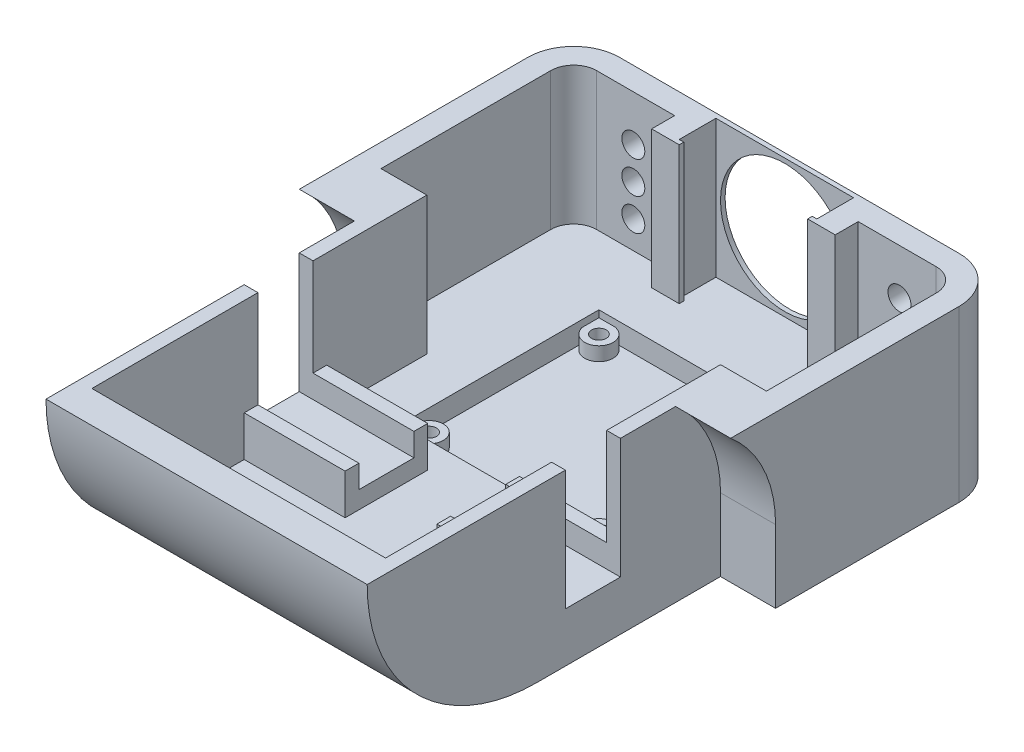
SolidWorks part; units mm, degrees
ref_plane "Front Plane" through (0, 0, 0) normal (0, 0, 1) x (1, 0, 0)
ref_plane "Top Plane" through (0, 0, 0) normal (0, 1, 0) x (1, 0, 0)
ref_plane "Right Plane" through (0, 0, 0) normal (1, 0, 0) x (0, 0, -1)
sketch "Sketch1" plane through (0, 0, 0) normal (0, 1, 0) x (1, 0, 0)
  line L0 (-18.5, 18.5) -> (-18.5, -18.5) construction
  line L1 (-18.5, -18.5) -> (18.5, -18.5) construction
  line L2 (18.5, -18.5) -> (18.5, 18.5) construction
  line L3 (18.5, 18.5) -> (-18.5, 18.5) construction
  line L4 (-21.5, 21.5) -> (-21.5, -21.5) construction
  line L5 (-21.5, -21.5) -> (21.5, -21.5) construction
  line L6 (21.5, -21.5) -> (21.5, 21.5) construction
  line L7 (-18.5, 18.5) -> (-21.5, 21.5) construction
  line L8 (-21.5, 21.5) -> (21.5, 21.5) construction
  line L9 (-18.5, -18.5) -> (-21.5, -21.5) construction
  line L10 (18.5, -18.5) -> (21.5, -21.5) construction
  line L11 (-18.5, 18.5) -> (0, 0) construction
  line L12 (0, 0) -> (18.5, -18.5) construction
  line L13 (-18.5, -18.5) -> (0, 0) construction
  line L14 (-35, -8.5) -> (-35, -48.5)
  line L15 (-35, -48.5) -> (35, -48.5)
  line L16 (35, -48.5) -> (35, -8.5)
  line L17 (35, -8.5) -> (47, -8.5)
  line L18 (47, -8.5) -> (47, 31.5)
  line L19 (-35, -8.5) -> (-47, -8.5)
  line L20 (-47, -8.5) -> (-47, 31.5)
  line L21 (-35, -8.5) -> (-21.5, 21.5) construction
  line L22 (21.5, 21.5) -> (35, -8.5) construction
  line L23 (-37, 41.5) -> (37, 41.5)
  line L24 (-21.6, -21.6) -> (21.6, -21.6)
  line L25 (21.6, -21.6) -> (21.6, 21.6)
  line L26 (-21.6, 21.6) -> (21.6, 21.6)
  line L27 (-21.6, 21.6) -> (-21.6, -21.6)
  line L28 (-21.5, -17.719) -> (-21.6, -17.719)
  line L29 (-17.719, -21.5) -> (-17.719, -21.6)
  line L30 (17.719, -21.5) -> (17.719, -21.6)
  line L31 (21.5, -17.719) -> (21.6, -17.719)
  line L32 (21.5, 17.719) -> (21.6, 17.719)
  line L33 (17.719, 21.5) -> (17.719, 21.6)
  line L34 (-21.5, 17.719) -> (-21.6, 17.719)
  line L35 (-17.719, 21.5) -> (-17.719, 21.6)
  circle A0 centre (-18.5, 18.5) radius 1.6
  circle A1 centre (18.5, 18.5) radius 1.6
  circle A2 centre (-18.5, -18.5) radius 1.6
  circle A3 centre (18.5, -18.5) radius 1.6
  arc A4 (-17.719, 21.5) -> (-21.5, 17.719) centre (-18.5, 18.5) cw
  arc A5 (-21.5, -17.719) -> (-17.719, -21.5) centre (-18.5, -18.5) cw
  arc A6 (17.719, -21.5) -> (21.5, -17.719) centre (18.5, -18.5) cw
  arc A7 (17.719, 21.5) -> (21.5, 17.719) centre (18.5, 18.5) ccw
  arc A8 (-47, 31.5) -> (-37, 41.5) centre (-37, 31.5) cw
  arc A9 (37, 41.5) -> (47, 31.5) centre (37, 31.5) cw
  dimension "D3" = 3.2
  dimension "D4" = 1.5
  dimension "D7" = 12
  dimension "D8" = 20
  dimension "D9" = 90
  dimension "D10" = 0.1
  dimension "D11" = 50
  dimension "D6" = 10
  dimension "D1" = 37
  dimension "D2" = 43
  dimension "D5" = 70
extrude "Boss-Extrude1" add sketch "Sketch1" against normal blind 7 contours L20 L19 L14 L15 L16 L17 L18 L4 L8 L6 L5 | A4 L8 L4 A0 | A0 | A7 L8 A4 L4 A5 L5 A6 L6 | A5 L4 L5 A2 | A2 | A6 L5 L6 A3 | A3 | L8 A7 L6 A1 | A1 region at (-41, 0, 7.1986) region at (-21.5123, 0, 19.6595) region at (0, 0, 0) region at (17.8067, 0, 21.55) region at (-21.5123, 0, -19.6595) region at (21.55, 0, -17.8067) region at (-18.5, 0, -18.5) region at (18.5, 0, -18.5) region at (-18.5, 0, 18.5) region at (18.5, 0, 18.5)
extrude "Cut-Extrude1" cut sketch "Sketch1<5>" against normal blind 1.5 contours A5 L4 L5 A2 | A2 | A7 L8 A4 L4 A5 L5 A6 L6 | A4 L8 L4 A0 | A0 | L8 A7 L6 A1 | A1 | A6 L5 L6 A3 | A3 region at (-21.5123, 0, 19.6595) region at (0, 0, 0) region at (17.8067, 0, 21.55) region at (-21.5123, 0, -19.6595) region at (21.55, 0, -17.8067) region at (-18.5, 0, -18.5) region at (18.5, 0, -18.5) region at (-18.5, 0, 18.5) region at (18.5, 0, 18.5)
sketch "Sketch1<5>" plane through (0, 0, 0) normal (0, 1, 0) x (1, 0, 0) same geometry as "Sketch1"
extrude "Cut-Extrude2" cut sketch "Sketch1<6>" against normal blind 3 from surface contours A7 L8 A4 L4 A5 L5 A6 L6 | A0 | A1 | A2 | A3 region at (0, 0, 0) region at (-18.5, 0, -18.5) region at (18.5, 0, -18.5) region at (-18.5, 0, 18.5) region at (18.5, 0, 18.5) starting at face at (0, -1.5, 0)
sketch "Sketch1<6>" plane through (0, 0, 0) normal (0, 1, 0) x (1, 0, 0) same geometry as "Sketch1"
sketch "Sketch3" plane through (0, 0, 0) normal (0, 1, 0) x (1, 0, 0)
  line L9 (47, -8.5) -> (47, 31.5) construction
  line L10 (-37, 41.5) -> (37, 41.5) construction
  line L11 (-47, -8.5) -> (-47, 31.5) construction
  line L18 (47, -8.5) -> (47, 31.5)
  line L19 (-37, 41.5) -> (37, 41.5)
  line L20 (-47, -8.5) -> (-47, 31.5)
  line L21 (-47, -8.5) -> (-42, -8.5)
  line L22 (42, -8.5) -> (47, -8.5)
  line L23 (-14, 41.5) -> (-14, 40.5)
  line L24 (-14, 40.5) -> (-15, 40.5)
  line L25 (-15, 40.5) -> (-15, 32.5)
  line L26 (-15, 32.5) -> (-14, 32.5)
  line L27 (-14, 32.5) -> (-14, 31.5)
  line L28 (14, 41.5) -> (14, 40.5)
  line L29 (14, 40.5) -> (15, 40.5)
  line L30 (15, 40.5) -> (15, 32.5)
  line L31 (15, 32.5) -> (14, 32.5)
  line L32 (14, 32.5) -> (14, 31.5)
  line L33 (-37, 31.5) -> (-15, 32.5) construction
  line L34 (15, 32.5) -> (37, 31.5) construction
  line L35 (-14, 31.5) -> (-20, 31.5)
  line L36 (-20, 31.5) -> (-20, 36.5)
  line L37 (-20, 36.5) -> (-37, 36.5)
  line L38 (-42, -8.5) -> (-42, 31.5)
  line L39 (-35, -8.5) -> (-47, -8.5) construction
  line L40 (14, 31.5) -> (20, 31.5)
  line L41 (20, 31.5) -> (20, 36.5)
  line L42 (20, 36.5) -> (37, 36.5)
  line L43 (42, -8.5) -> (42, 31.5)
  arc A6 (47, 31.5) -> (37, 41.5) centre (37, 31.5) ccw construction
  arc A7 (-37, 41.5) -> (-47, 31.5) centre (-37, 31.5) ccw construction
  arc A8 (47, 31.5) -> (37, 41.5) centre (37, 31.5) ccw
  arc A9 (-37, 41.5) -> (-47, 31.5) centre (-37, 31.5) ccw
  arc A10 (-42, 31.5) -> (-37, 36.5) centre (-37, 31.5) cw
  arc A11 (37, 36.5) -> (42, 31.5) centre (37, 31.5) cw
  arc M13 (47, 31.5) -> (37, 41.5) centre (37, 31.5) ccw
  line M14 (37, 41.5) -> (-37, 41.5)
  arc M15 (-37, 41.5) -> (-47, 31.5) centre (-37, 31.5) ccw
  line M16 (-47, 31.5) -> (-47, -8.5)
  line M17 (-47, -8.5) -> (-35, -8.5)
  line M21 (35, -8.5) -> (47, -8.5)
  line M22 (47, -8.5) -> (47, 31.5)
  dimension "D2" = 30
  dimension "D3" = 8
  dimension "D4" = 1
  dimension "D1" = 1
  dimension "D5" = 5
  dimension "D6" = 5
extrude "Boss-Extrude2" add sketch "Sketch3" along normal blind 30 contours L27 L26 L25 L24 L23 L19 M15 M16 M17 | L31 L32 L28 L29 L30 M21 M22 M13 M14 region at (44.5, 0, 7.9009) region at (-14.5991, 0, -41)
sketch "Sketch5" plane through (0, 0, 0) normal (1, 0, 0) x (0, 0, -1)
  line L0 (-48.5, 0) -> (-48.5, -7)
  line L1 (-78.5, 30) -> (-85.5, 30)
  line L2 (31.5, 30) -> (-8.5, 30) construction
  line L3 (-48.5, 0) -> (-43.4308, 0) construction
  line L4 (-8.5, 0) -> (-48.5, 0) construction
  line L5 (-78.5, 30) -> (-78.5, 34.1499) construction
  arc A0 (-48.5, 0) -> (-78.5, 30) centre (-48.5, 30) cw
  arc A1 (-48.5, -7) -> (-85.5, 30) centre (-48.5, 30) cw
extrude "Boss-Extrude3" add sketch "Sketch5" against normal up to surface and the other way up to surface up to face at (-35, -3.5, 28.5) other way up to face at (35, -3.5, 28.5)
ref_plane "Plane1" through (0, -24.25, 24.25) normal (0, -0.7071, 0.7071) x (-1, 0, 0)
sketch "Sketch6" plane through (0, -24.25, 24.25) normal (0, -0.7071, 0.7071) x (-1, 0, 0)
  line L0 (-21.59, -65.9179) -> (-14.99, -63.4179) construction
  line L1 (-21.59, -65.9179) -> (21.59, -65.9179) construction
  line L2 (-21.59, -65.9179) -> (-21.59, -45.0979) construction
  line L3 (-21.59, -45.0979) -> (21.59, -45.0979) construction
  line L4 (21.59, -65.9179) -> (21.59, -45.0979) construction
  line L5 (-35, -34.2947) -> (-21.59, -45.0979) construction
  line L6 (14.99, -47.5979) -> (21.59, -45.0979) construction
  line L7 (-21.59, -45.0979) -> (14.99, -47.5979) construction
  line L8 (-14.99, -63.4179) -> (21.59, -65.9179) construction
  line L9 (-35, -76.7211) -> (-21.59, -65.9179) construction
  line L10 (21.59, -65.9179) -> (35, -76.7211) construction
  line L11 (-21.59, -64.4179) -> (21.59, -64.4179)
  line L12 (-21.59, -46.5979) -> (21.59, -46.5979)
  line L13 (-21.69, -66.0179) -> (-21.69, -44.9979)
  line L14 (-21.69, -44.9979) -> (21.69, -44.9979)
  line L15 (21.69, -66.0179) -> (21.69, -44.9979)
  line L16 (-21.69, -66.0179) -> (21.69, -66.0179)
  line L17 (-21.59, -64.4179) -> (-21.69, -64.4179)
  line L18 (-21.59, -46.5979) -> (-21.69, -46.5979)
  line L19 (21.59, -46.5979) -> (21.69, -46.5979)
  line L20 (21.59, -64.4179) -> (21.69, -64.4179)
  circle A0 centre (-14.99, -63.4179) radius 1.5
  circle A1 centre (14.99, -47.5979) radius 1.5
  arc A2 (-17.8184, -64.4179) -> (-12.1616, -64.4179) centre (-14.99, -63.4179) cw
  arc A3 (17.8184, -46.5979) -> (12.1616, -46.5979) centre (14.99, -47.5979) cw
  dimension "D5" = 3
  dimension "D8" = 1.5
  dimension "D1" = 43.18
  dimension "D2" = 20.82
  dimension "D3" = 6.6
  dimension "D4" = 2.5
  dimension "D6" = 1.5
  dimension "D7" = 1.5
  dimension "D9" = 0.1
extrude "Cut-Extrude3" cut sketch "Sketch6" along normal blind 9 contours A1 L12 L4 L3 L2 | L12 A1 | L12 A1 | A3 L12 A1 | L12 A3 L2 L11 A2 L4 | A2 L11 A0 | L11 A0 | A0 L11 L2 L1 L4 | L11 A0 region at (0, 15, 63.5) region at (-0.1691, 21.8708, 70.3708) region at (14.99, 18.5229, 67.0229) region at (14.99, 20.4885, 68.9885) region at (14.99, 21.444, 69.944) region at (0.1691, 8.1292, 56.6292) region at (-13.0168, 8.7507, 57.2507) region at (-14.99, 8.556, 57.056) region at (-14.99, 9.5115, 58.0115)
extrude "Cut-Extrude4" cut sketch "Sketch6<3>" along normal blind 3 from surface contours L12 A1 | L12 A1 | L12 A3 L2 L11 A2 L4 | L11 A0 | L11 A0 region at (0, 15, 63.5) region at (14.99, 20.4885, 68.9885) region at (14.99, 21.444, 69.944) region at (-14.99, 8.556, 57.056) region at (-14.99, 9.5115, 58.0115) starting at face at (0, 8.636, 69.864)
sketch "Sketch6<3>" plane through (0, -24.25, 24.25) normal (0, -0.7071, 0.7071) x (-1, 0, 0) same geometry as "Sketch6"
sketch "Sketch7" plane through (0, 0, 0) normal (0, 1, 0) x (1, 0, 0)
  line L0 (35, -8.5) -> (42, -8.5) construction
  line L1 (35, -48.5) -> (35, -8.5) construction
  line L2 (-35, -8.5) -> (-35, -48.5) construction
  line L3 (-35, -8.5) -> (-42, -8.5) construction
  line L4 (35, -8.5) -> (42, -8.5)
  line L5 (35, -48.5) -> (35, -8.5)
  line L6 (-35, -8.5) -> (-35, -48.5)
  line L7 (-35, -8.5) -> (-42, -8.5)
  line L8 (32, -48.5) -> (32, -5.5)
  line L9 (32, -5.5) -> (42, -5.5)
  line L10 (-32, -5.5) -> (-42, -5.5)
  line L11 (-32, -5.5) -> (-32, -48.5)
  line L12 (42, -5.5) -> (42, -8.5)
  line L13 (35, -48.5) -> (32, -48.5)
  line L14 (-32, -48.5) -> (-35, -48.5)
  line L15 (-42, -5.5) -> (-42, -8.5)
  line M9 (35, -8.5) -> (42, -8.5)
  line M25 (-42, -8.5) -> (-35, -8.5)
  line M26 (-35, -8.5) -> (-35, -48.5)
  line M27 (-35, -48.5) -> (35, -48.5)
  line M28 (35, -48.5) -> (35, -8.5)
  dimension "D1" = 3
extrude "Boss-Extrude4" add sketch "Sketch7" along normal up to surface (30 mm away) contours L11 L10 M25 M26 M27 | L9 L8 M27 M28 M9 region at (34.2, 0, 24.2) region at (-34.2, 0, 24.2) up to face at (-27.2219, 30, -29.579)
sketch "Sketch8" plane through (0, 0, 48.5) normal (0, 0, 1) x (1, 0, 0)
  line L0 (35, 30) -> (32, 30) construction
  line L1 (32, 30) -> (32, 0) construction
  line L2 (32, 0) -> (35, 0) construction
  line L3 (35, 0) -> (35, 30) construction
  line L4 (-32, 30) -> (-35, 30) construction
  line L5 (-35, 30) -> (-35, 0) construction
  line L6 (-35, 0) -> (-32, 0) construction
  line L7 (-32, 0) -> (-32, 30) construction
  line L8 (35, 30) -> (32, 30)
  line L9 (32, 30) -> (32, 0)
  line L10 (32, 0) -> (35, 0)
  line L11 (35, 0) -> (35, 30)
  line L12 (-32, 30) -> (-35, 30)
  line L13 (-35, 30) -> (-35, 0)
  line L14 (-35, 0) -> (-32, 0)
  line L15 (-32, 0) -> (-32, 30)
extrude "Boss-Extrude6" add sketch "Sketch8" along normal up to surface up to face at (0, 9.459, 69.041)
sketch "Sketch9" plane through (0, 0, -41.5) normal (0, 0, -1) x (-1, 0, 0)
  line L0 (-29, 6) -> (-29, 13) construction
  line L1 (-29, 13) -> (-29, 20) construction
  line L2 (29, 20) -> (29, 13) construction
  line L3 (29, 13) -> (29, 6) construction
  line L4 (-37, 30) -> (-29, 20) construction
  line L5 (-29, 20) -> (-14, 30) construction
  line L6 (14, 30) -> (29, 20) construction
  line L7 (29, 20) -> (37, 30) construction
  line L8 (-14, 30) -> (-14, 0) construction
  line L9 (-37, 30) -> (-14, 30) construction
  circle A0 centre (-29, 20) radius 2.5
  circle A1 centre (-29, 13) radius 2.5
  circle A2 centre (-29, 6) radius 2.5
  circle A3 centre (29, 20) radius 2.5
  circle A4 centre (29, 13) radius 2.5
  circle A5 centre (29, 6) radius 2.5
  dimension "D1" = 5
  dimension "D2" = 7
  dimension "D3" = 15
  dimension "D4" = 10
extrude "Cut-Extrude5" cut sketch "Sketch9" against normal up to surface (5 mm away) contours A0 | A1 | A2 | A3 | A4 | A5 region at (29, 20, -41.5) region at (29, 13, -41.5) region at (29, 6, -41.5) region at (-29, 20, -41.5) region at (-29, 13, -41.5) region at (-29, 6, -41.5) up to face at (-28.5, 15, -36.5)
sketch "Sketch10" plane through (0, 0, 0) normal (1, 0, 0) x (0, 0, -1)
  line L0 (-30.3125, 30) -> (-30.3125, 3.8125)
  line L1 (-8.5, 30) -> (-85.5, 30) construction
  line L2 (-42.3125, 30) -> (-42.3125, 3.8125)
  line L3 (-36.3125, 8.8125) -> (-36.3125, -15) construction
  line L4 (-36.3125, 8.8125) -> (-12.5, 8.8125) construction
  line L5 (-8.5, -7) -> (-48.5, -7) construction
  line L6 (-8.5, -7) -> (-8.5, 30) construction
  line L7 (-30.3125, 30) -> (-42.3125, 30)
  line L8 (-30.3125, 3.8125) -> (-42.3125, 3.8125)
  line L9 (-30.3125, 3.8125) -> (-36.3125, 8.8125) construction
  line L10 (-36.3125, 8.8125) -> (-42.3125, 13.8125) construction
  line L11 (-36.3125, 8.8125) -> (-42.3125, 3.8125) construction
  line L12 (-27.3125, 0) -> (-45.3125, 0)
  line L13 (-27.3125, 0) -> (-27.3125, 8.8125)
  line L14 (-27.3125, 8.8125) -> (-30.3125, 8.8125)
  line L15 (-42.3125, 8.8125) -> (-45.3125, 8.8125)
  line L16 (-45.3125, 8.8125) -> (-45.3125, 0)
  line L17 (-5.5, 0) -> (31.5, 0) construction
  line L18 (-8.5, 8.8125) -> (-8.5, 30)
  line L19 (-8.5, -7) -> (-8.5, 30) construction
  line L20 (-8.5, 30) -> (-18.2951, 30)
  circle A1 centre (-36.3125, 8.8125) radius 23.8125 construction
  arc A2 (-8.5, 8.8125) -> (-18.2951, 30) centre (-36.3125, 8.8125) ccw
  dimension "D1" = 47.625
  dimension "D4" = 12
  dimension "D2" = 8
  dimension "D3" = 4
  dimension "D5" = 5
  dimension "D6" = 3
  dimension "D7" = 5
extrude "Cut-Extrude6" cut sketch "Sketch10" against normal through all both and the other way through all contours L8 L0 L7 L2 region at (0, 16.9062, 36.3125)
extrude "Boss-Extrude7" add sketch "Sketch10<3>" along normal up to surface (32 mm away) from offset 10 contours L15 L16 L12 L13 L14 L0 L8 L2 region at (0, 3.2466, 36.3125) up to face at (32, 15.1765, 36.1829)
sketch "Sketch10<3>" plane through (0, 0, 0) normal (1, 0, 0) x (0, 0, -1) same geometry as "Sketch10"
extrude "Boss-Extrude8" add sketch "Sketch10<4>" against normal up to surface (32 mm away) from offset 10 contours L15 L16 L12 L13 L14 L0 L8 L2 region at (0, 3.2466, 36.3125) up to face at (-32, 15.1765, 36.1829) offset against normal yes
sketch "Sketch10<4>" plane through (0, 0, 0) normal (1, 0, 0) x (0, 0, -1) same geometry as "Sketch10"
extrude "Boss-Extrude9" add sketch "Sketch10<5>" against normal up to surface (47 mm away) from surface contours A2 L18 L20 region at (0, 24.9078, 11.3221) up to face at (-47, 11.5, -11.5) starting at face at (-35, 13.2453, 37.9891)
sketch "Sketch10<5>" plane through (0, 0, 0) normal (1, 0, 0) x (0, 0, -1) same geometry as "Sketch10"
extrude "Boss-Extrude10" add sketch "Sketch10<6>" along normal up to surface (47 mm away) from surface contours A2 L18 L20 region at (0, 24.9078, 11.3221) up to face at (47, 11.5, -11.5) starting at face at (35, 13.2453, 37.9891)
sketch "Sketch10<6>" plane through (0, 0, 0) normal (1, 0, 0) x (0, 0, -1) same geometry as "Sketch10"
sketch "Sketch12" plane through (0, -7, 0) normal (0, -1, 0) x (1, 0, 0)
  line L0 (-22.5, -16.5) -> (22.5, -16.5) construction
  line L1 (-13.5, -11.3038) -> (-22.5, -6.1077)
  line L2 (-22.5, -6.1077) -> (-31.5, -11.3038)
  line L3 (-31.5, -11.3038) -> (-31.5, -21.6962)
  line L4 (-31.5, -21.6962) -> (-22.5, -26.8923)
  line L5 (-22.5, -26.8923) -> (-13.5, -21.6962)
  line L6 (-13.5, -21.6962) -> (-13.5, -11.3038)
  line L7 (31.5, -11.3038) -> (22.5, -6.1077)
  line L8 (22.5, -6.1077) -> (13.5, -11.3038)
  line L9 (13.5, -11.3038) -> (13.5, -21.6962)
  line L10 (13.5, -21.6962) -> (22.5, -26.8923)
  line L11 (22.5, -26.8923) -> (31.5, -21.6962)
  line L12 (31.5, -21.6962) -> (31.5, -11.3038)
  line L13 (22.5, -16.5) -> (0, 0) construction
  line L14 (0, 0) -> (-22.5, -16.5) construction
  line L15 (-37, -41.5) -> (37, -41.5) construction
  circle A0 centre (-22.5, -16.5) radius 9 construction
  circle A1 centre (22.5, -16.5) radius 9 construction
  dimension "D1" = 18
  dimension "D2" = 45
  dimension "D3" = 25
extrude "Boss-Extrude11" add sketch "Sketch12" along normal blind 5
chamfer "Chamfer1" distance 5 angle 45 12 edges at (27, -7, -8.7058) (18, -7, -8.7058) (13.5, -7, -16.5) (18, -7, -24.2942) (27, -7, -24.2942) (31.5, -7, -16.5) (-18, -7, -8.7058) (-27, -7, -8.7058) (-31.5, -7, -16.5) (-27, -7, -24.2942) (-18, -7, -24.2942) (-13.5, -7, -16.5)
sketch "Sketch13" plane through (0, 0, -41.5) normal (0, 0, -1) x (-1, 0, 0)
  line L0 (-14, 30) -> (-14, 0) construction
  line L1 (14, 30) -> (14, 0) construction
  line L4 (-14, 0) -> (0, 15) construction
  line L5 (0, 15) -> (-14, 30) construction
  line L6 (-14, 30) -> (14, 30)
  line L7 (14, 30) -> (14, 0)
  line L8 (14, 0) -> (-14, 0)
  line L9 (-14, 0) -> (-14, 30)
  circle A0 centre (0, 15) radius 14
  line M10 (14, 30) -> (14, 0)
  line M11 (14, 0) -> (-14, 0)
  line M12 (-14, 0) -> (-14, 30)
extrude "Boss-Extrude12" add sketch "Sketch13" against normal up to surface (1 mm away) contours A0 L6 L9 M10 | A0 L7 M12 M11 region at (0, 29.6824, -41.5) region at (0, 0.6824, -41.5) up to face at (14.5, 15, -40.5)
